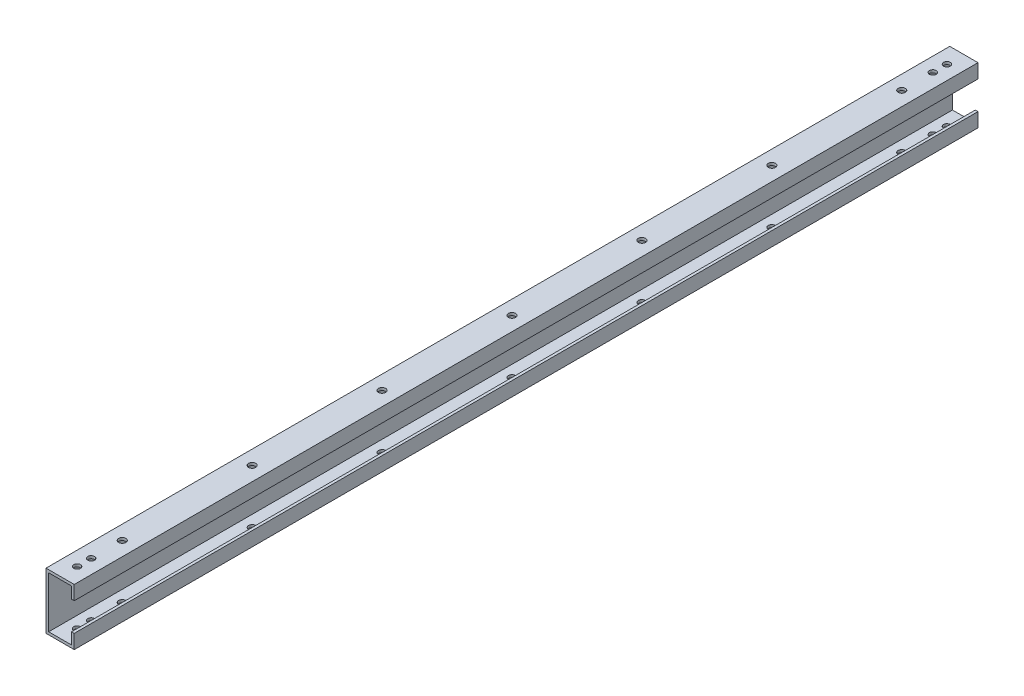
SolidWorks part; units mm, degrees
material "AISI 1020 Acero laminado en frío"
ref_plane "Alzado" through (0, 0, 0) normal (0, 0, 1) x (1, 0, 0)
ref_plane "Planta" through (0, 0, 0) normal (0, 1, 0) x (1, 0, 0)
ref_plane "Vista lateral" through (0, 0, 0) normal (1, 0, 0) x (0, 0, -1)
sketch "Croquis1" plane through (0, 0, 0) normal (0, 0, 1) x (1, 0, 0)
  line L0 (-20.2375, -45.2375) -> (-20.2375, 45.2375)
  line L1 (-25, -50) -> (25, -50)
  line L2 (-25, -50) -> (-25, 50)
  line L3 (-25, 50) -> (25, 50)
  line L4 (25, -50) -> (25, 50)
  line L5 (-25, -50) -> (25, 50) construction
  line L6 (-25, 50) -> (25, -50) construction
  line L7 (-20.2375, 45.2375) -> (20.2375, 45.2375)
  line L8 (20.2375, -45.2375) -> (20.2375, 45.2375)
  line L9 (-20.2375, -45.2375) -> (20.2375, -45.2375)
  point P0 (0, 0)
  dimension "D1" = 100
  dimension "D2" = 50
  dimension "D3" = 4.7625
extrude "Saliente-Extruir1" add sketch "Croquis1" along normal mid plane 1600
sketch "Croquis2" plane through (25, 0, 0) normal (1, 0, 0) x (0, 0, -1)
  line L1 (800, 25) -> (-800, 25)
  line L2 (800, 25) -> (800, -25)
  line L3 (800, -25) -> (-800, -25)
  line L4 (-800, 25) -> (-800, -25)
  line L5 (800, 25) -> (-800, -25) construction
  line L6 (800, -25) -> (-800, 25) construction
  point P0 (0, 0)
  dimension "D1" = 1600
  dimension "D2" = 50
extrude "Cortar-Extruir1" cut sketch "Croquis2" against normal blind 5
sketch "Croquis8" plane through (25, 50, 0) normal (0, -1, 0) x (0, 0, 1)
  line L0 (850.2048, 25) -> (-1024.1629, 25) construction
  line L1 (0, 25) -> (230, 25) construction
  line L2 (0, 25) -> (-230, 25) construction
  circle A0 centre (0, 25) radius 6.35
  circle A1 centre (230, 25) radius 6.35
  circle A2 centre (460, 25) radius 6.35
  circle A3 centre (690, 25) radius 6.35
  circle A4 centre (920, 25) radius 6.35
  circle A5 centre (1150, 25) radius 6.35
  circle A6 centre (1380, 25) radius 6.35
  circle A7 centre (1610, 25) radius 6.35
  circle A8 centre (-230, 25) radius 6.35
  circle A9 centre (-460, 25) radius 6.35
  circle A10 centre (-690, 25) radius 6.35
  circle A11 centre (-920, 25) radius 6.35
  circle A12 centre (-1150, 25) radius 6.35
  circle A13 centre (-1380, 25) radius 6.35
  circle A14 centre (-1610, 25) radius 6.35
  dimension "D1" = 12.7
  dimension "D3" = 230
  dimension "D5" = 230
  dimension "D2" = 8
  dimension "D4" = 8
extrude "Cortar-Extruir2" cut sketch "Croquis8" along normal blind 130
hole_wizard "Taladro de margen para 7/161" positions "Croquis9" profile "Croquis10" hole size "7/16" standard "Ansi Inch"
sketch "Croquis9" plane through (349.3117, -55.2375, 12.2412) normal (0, -1, 0) x (-1, 0, 0)
  point P0 (-600.6883, 757.2412)
  point P3 (-600.6883, 782.2412)
  point P6 (349.3117, 782.2412)
  point P9 (349.3117, 757.2412)
sketch "Croquis10" plane through (950, -55.2375, -745) normal (1, 0, 0) x (0, 0, -1)
  line L0 (0, 0) -> (0, 155.0766)
  line L1 (0, 155.0766) -> (5.9525, 151.5)
  line L2 (5.9525, 151.5) -> (5.9525, 0)
  line L3 (5.9525, 0) -> (0, 0)
  line L4 (0, 155.0766) -> (-5.9525, 151.5) construction
  line L5 (0, -6.35) -> (0, 107.95) construction
  dimension "Diámetro de taladro" = 11.905
  dimension "Profundidad de taladro" = 151.5
  dimension "Ángulo de perforador" = 118
hole_wizard "Taladro de margen para 7/162" positions "Croquis11" profile "Croquis12" hole size "7/16" standard "Ansi Inch"
sketch "Croquis11" plane through (600.6883, -55.2375, -12.2412) normal (0, -1, 0) x (1, 0, 0)
  point P0 (-600.6883, 757.2412)
  point P3 (-600.6883, 782.2412)
  point P6 (349.3117, 782.2412)
  point P9 (349.3117, 757.2412)
sketch "Croquis12" plane through (0, -55.2375, 745) normal (1, 0, 0) x (0, 0, -1)
  line L0 (0, 0) -> (0, 155.0766)
  line L1 (0, 155.0766) -> (5.9525, 151.5)
  line L2 (5.9525, 151.5) -> (5.9525, 0)
  line L3 (5.9525, 0) -> (0, 0)
  line L4 (0, 155.0766) -> (-5.9525, 151.5) construction
  line L5 (0, -6.35) -> (0, 107.95) construction
  dimension "Diámetro de taladro" = 11.905
  dimension "Profundidad de taladro" = 151.5
  dimension "Ángulo de perforador" = 118
